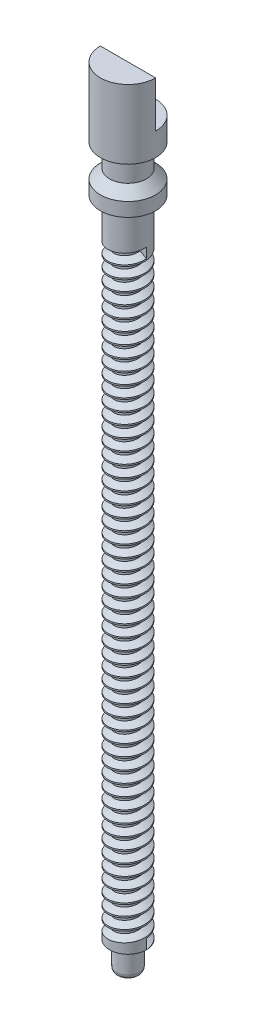
SolidWorks part; units mm, degrees
ref_plane "Front Plane" through (0, 0, 0) normal (0, 0, 1) x (1, 0, 0)
ref_plane "Top Plane" through (0, 0, 0) normal (0, 1, 0) x (1, 0, 0)
ref_plane "Right Plane" through (0, 0, 0) normal (1, 0, 0) x (0, 0, -1)
sketch "Sketch1" plane through (0, 0, 0) normal (0, 0, 1) x (1, 0, 0)
  line L0 (0, 0) -> (0, 17.1) construction
  line L1 (0, 0) -> (0.25, 0)
  line L2 (0.25, 0) -> (0.25, 0.6)
  line L3 (0.25, 0.6) -> (0.4, 0.6)
  line L4 (0.4, 0.6) -> (0.4, 13.6)
  line L5 (0.4, 13.6) -> (0.4, 14.6)
  line L6 (0.4, 14.6) -> (0.6, 14.6)
  line L7 (0.6, 14.6) -> (0.6, 14.9)
  line L8 (0.6, 14.9) -> (0.4, 15.1)
  line L9 (0.4, 15.1) -> (0.4, 15.6)
  line L10 (0.4, 15.6) -> (0.6, 15.6)
  line L11 (0.6, 15.6) -> (0.6, 17.1)
  line L12 (0.6, 17.1) -> (0, 17.1)
  line L13 (0, 17.1) -> (0, 0)
  dimension "D1" = 17.1
  dimension "D2" = 0.25
  dimension "D3" = 0.6
  dimension "D4" = 0.4
  dimension "D5" = 13
  dimension "D6" = 1
  dimension "D7" = 0.3
  dimension "D8" = 0.2
  dimension "D9" = 0.5
  dimension "D10" = 1.5
  dimension "D11" = 0.6
revolve "Revolve1" add sketch "Sketch1" angle 360 about L0
fillet "Fillet2" radius 0.1 1 edges at (0, 0, -0.25)
thread "Thread1" pitch 0.25 profile "Thread Profile2" start angle 0, offset 0.0001, length 13, pitch 0.25, diameter 0.8
ref_plane "Plane2" through (0.4, 0.5999, 0) normal (0, 0, 1) x (1, 0, 0)
sketch "Thread Profile2" plane through (0.4, 0.5999, 0) normal (0, 0, 1) x (1, 0, 0)
  line L0 (0, 0) -> (0, 0.25) construction
  line L11 (0, 0) -> (0, 0.2187)
  line L12 (0, 0.2187) -> (-0.1353, 0.1406)
  line L13 (-0.1353, 0.1406) -> (-0.1353, 0.0781)
  line L15 (-0.1353, 0.0781) -> (0, 0)
  line L17 (-0.1353, 0.1094) -> (0, 0.1094) construction
  point P2 (0, 0)
  dimension "Pitch" = 0.25
  dimension "Profile_Angle" = 60
  dimension "Profile_Land" = 0.0625
  dimension "Profile_Height" = 0.1353
sketch "Sketch3" plane through (0, 17.1, 0) normal (0, 1, 0) x (1, 0, 0)
  line L0 (-0.6, 0) -> (0.6, 0)
  arc A0 (-0.6, 0) -> (0.6, 0) centre (0, 0) cw
  circle A1 centre (0, 0) radius 0.6 construction
extrude "Cut-Extrude1" cut sketch "Sketch3" against normal blind 1
